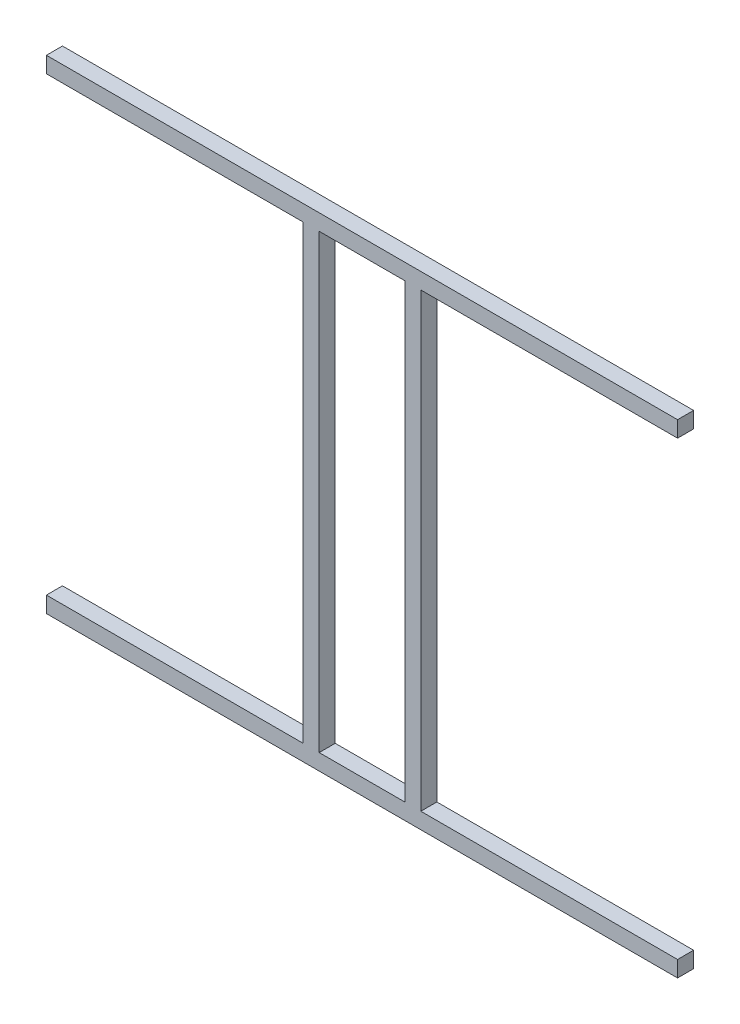
SolidWorks part; units mm, degrees
ref_plane "前视基准面" through (0, 0, 0) normal (0, 0, 1) x (1, 0, 0)
ref_plane "上视基准面" through (0, 0, 0) normal (0, 1, 0) x (1, 0, 0)
ref_plane "右视基准面" through (0, 0, 0) normal (1, 0, 0) x (0, 0, -1)
sketch "Sketch1" plane through (0, 0, 0) normal (0, 0, 1) x (1, 0, 0)
  line L0 (57, 0) -> (129.8959, 0) construction
  line L1 (57, 54.0142) -> (57, -54.0142) construction
  line L2 (85, 100.4999) -> (85, 76) construction
  line L3 (55, 100.9999) -> (-55, 100.9999)
  line L4 (55, 100.9999) -> (55, 85.9999)
  line L5 (55, 85.9999) -> (-55, 85.9999)
  line L6 (-55, 100.9999) -> (-55, 85.9999)
  line L7 (-85, 76) -> (-85, 100.4999) construction
  line L8 (-55, -100.9999) -> (-55, -85.9999)
  line L9 (55, -85.9999) -> (-55, -85.9999)
  line L10 (55, -100.9999) -> (55, -85.9999)
  line L11 (55, -100.9999) -> (-55, -100.9999)
  circle A0 centre (35, 93.4999) radius 2.1 construction
  dimension "D2" = 7.5
  dimension "D1" = 15
  dimension "D3" = 30
  dimension "D4" = 30
extrude "Extrude1" add sketch "Sketch1" along normal blind 5
sketch "Sketch2" plane through (0, 0, 5) normal (0, 0, 1) x (1, 0, 0)
  line L0 (55, -100.9999) -> (55, -85.9999) construction
  line L2 (55, -210.9999) -> (55, 210.9999)
  line L4 (40, -210.9999) -> (40, 210.9999)
  line L6 (-55, -210.9999) -> (-55, 210.9999)
  line L8 (-40, -210.9999) -> (-40, 210.9999)
  line L9 (-55, -85.9999) -> (-55, -100.9999) construction
  line L12 (-40, 210.9999) -> (40, 210.9999)
  line L13 (-295, -210.9999) -> (-55, -210.9999)
  line L14 (-295, -210.9999) -> (-295, -225.9999)
  line L15 (-295, -225.9999) -> (295, -225.9999)
  line L16 (295, -210.9999) -> (295, -225.9999)
  line L17 (-295, 210.9999) -> (-55, 210.9999)
  line L18 (-295, 210.9999) -> (-295, 225.9999)
  line L19 (-295, 225.9999) -> (295, 225.9999)
  line L20 (295, 210.9999) -> (295, 225.9999)
  line L21 (55, 210.9999) -> (295, 210.9999)
  line L22 (55, -210.9999) -> (295, -210.9999)
  line L23 (-40, -210.9999) -> (40, -210.9999)
  dimension "D1" = 15
  dimension "D2" = 15
  dimension "D5" = 590
  dimension "D6" = 240
  dimension "D7" = 15
  dimension "D8" = 15
extrude "Extrude2" add sketch "Sketch2" along normal blind 15
sketch "Sketch3" plane through (0, 0, 5) normal (0, 0, -1) x (-1, 0, 0)
  line L1 (-193.5809, 217.091) -> (203.3591, 217.091)
  line L2 (-193.5809, 217.091) -> (-193.5809, -139.5383)
  line L3 (-193.5809, -139.5383) -> (203.3591, -139.5383)
  line L4 (203.3591, 217.091) -> (203.3591, -139.5383)
extrude "Cut-Extrude1" cut sketch "Sketch3" along normal blind 10
